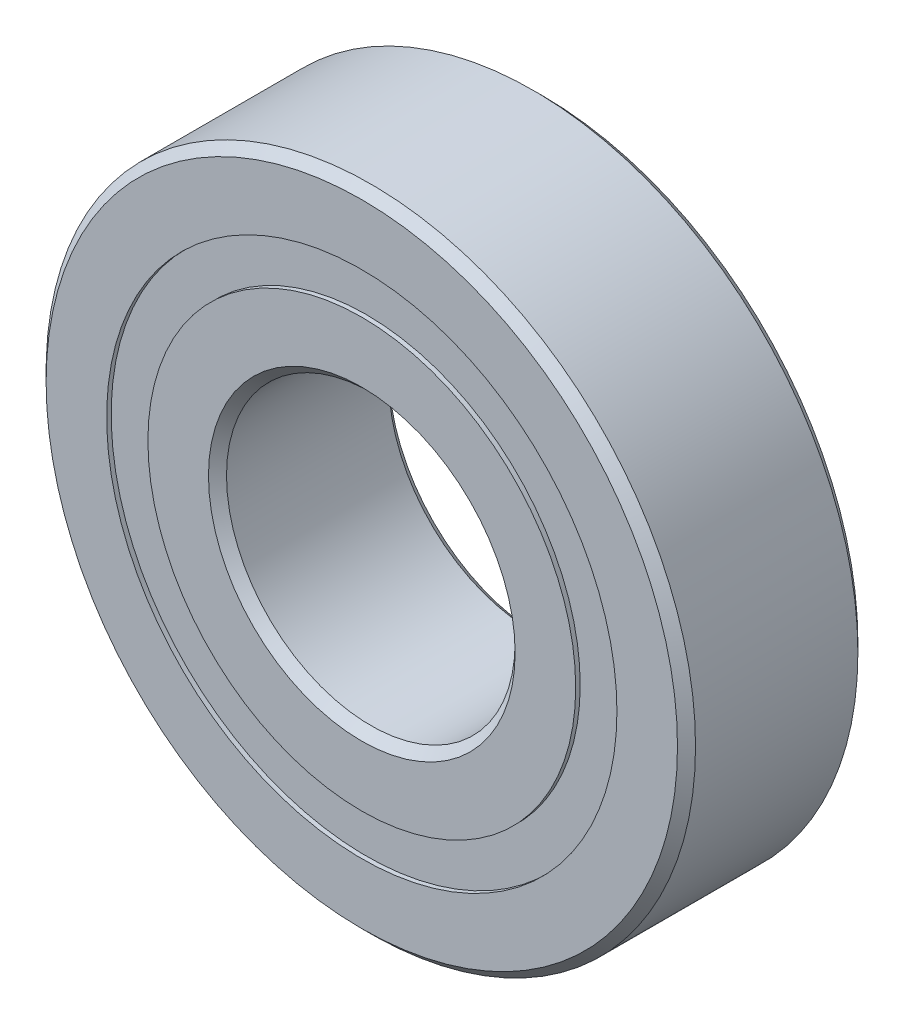
SolidWorks part; units mm, degrees
ref_plane "Front Plane" through (0, 0, 0) normal (0, 0, 1) x (1, 0, 0)
ref_plane "Top Plane" through (0, 0, 0) normal (0, 1, 0) x (1, 0, 0)
ref_plane "Right Plane" through (0, 0, 0) normal (1, 0, 0) x (0, 0, -1)
sketch "Sketch1" plane through (0, 0, 0) normal (1, 0, 0) x (0, 0, -1)
  line L0 (-3.9688, 0) -> (3.9688, 0) construction
  line L1 (0, 14.2875) -> (0, -14.2875) construction
  line L2 (3.5719, 14.2875) -> (-3.5719, 14.2875)
  line L3 (-3.5719, 14.2875) -> (-3.9688, 13.8906)
  line L4 (-3.9688, 13.8906) -> (-3.9688, 11.2259)
  line L5 (-3.9688, 11.2259) -> (-1.7639, 11.2259)
  line L6 (3.9687, 11.2259) -> (1.7639, 11.2259)
  line L7 (3.9687, 13.8906) -> (3.9687, 11.2259)
  line L8 (3.5719, 14.2875) -> (3.9687, 13.8906)
  line L9 (0, 14.2875) -> (0, 10.3187) construction
  line L10 (0, 10.3187) -> (0, 6.35) construction
  arc A0 (-1.7639, 11.2259) -> (1.7639, 11.2259) centre (0, 10.3187) cw
  point P14 (0, 6.35)
  dimension "Width" = 7.9375
  dimension "OD" = 28.575
  dimension "D1" = 45
  dimension "D2" = 0.3969
  dimension "Shaft Dia" = 12.7
  dimension "D3" = 3.5278
  dimension "D4" = 0.9071
revolve "Revolve1" add sketch "Sketch1" angle 360 about L0
sketch "Sketch3" plane through (0, 0, 0) normal (1, 0, 0) x (0, 0, -1)
  line L0 (-3.9688, 9.4116) -> (-1.7639, 9.4116)
  line L1 (0, 14.2875) -> (0, -14.2875) construction
  line L2 (-3.9688, 13.8906) -> (-3.9688, 11.2259) construction
  line L3 (-3.9688, 9.4116) -> (-3.9688, 6.7469)
  line L4 (-3.5719, 14.2875) -> (-3.9688, 13.8906) construction
  line L5 (-3.9688, 6.7469) -> (-3.5719, 6.35)
  line L6 (-3.5719, 6.35) -> (3.5719, 6.35)
  line L7 (3.5719, 14.2875) -> (3.5719, -14.2875) construction
  line L8 (3.5719, 6.35) -> (3.9688, 6.7469)
  line L9 (3.9688, -13.8906) -> (3.9688, 13.8906) construction
  line L10 (3.9688, 6.7469) -> (3.9688, 9.4116)
  line L11 (3.9688, 9.4116) -> (1.7639, 9.4116)
  line L13 (3.5719, 14.2875) -> (3.9687, 13.8906) construction
  arc A0 (1.7639, 11.2259) -> (-1.7639, 11.2259) centre (0, 10.3187) ccw construction
  arc A1 (1.7639, 9.4116) -> (-1.7639, 9.4116) centre (0, 10.3187) cw
revolve "Revolve3" add sketch "Sketch3" angle 360 about L0
sketch "Sketch4" plane through (0, 0, 0) normal (1, 0, 0) x (0, 0, -1)
  line L0 (-1.9835, 10.3187) -> (1.9835, 10.3187)
  arc A2 (-1.9835, 10.3187) -> (1.9835, 10.3187) centre (0, 10.3187) cw
  arc A3 (1.7639, 11.2259) -> (-1.7639, 11.2259) centre (0, 10.3187) ccw construction
revolve "Revolve4" add sketch "Sketch4" angle 360 about L0
ref_axis "Axis1" through (0, 0, -3.9688) along (0, 0, 1)
pattern_circular "CirPattern1" count 10 every 36 about axis through (0, 0, -3.9688) along (0, 0, 1) of bodies 104
sketch "Sketch5" plane through (0, 0, 0) normal (1, 0, 0) x (0, 0, -1)
  line L0 (-3.9688, 11.2259) -> (-1.7639, 11.2259) construction
  line L1 (-3.7703, 11.2259) -> (-1.9835, 11.2259)
  line L2 (-3.7703, 11.2259) -> (-3.7703, 9.4116)
  line L3 (-3.7703, 9.4116) -> (-1.9835, 9.4116)
  line L4 (-1.9835, 11.2259) -> (-1.9835, 9.4116)
  line L5 (-3.9688, 9.4116) -> (-1.7639, 9.4116) construction
  line L6 (3.9687, 11.2259) -> (1.7639, 11.2259) construction
  line L7 (3.7703, 11.2259) -> (1.9835, 11.2259)
  line L8 (3.7703, 11.2259) -> (3.7703, 9.4116)
  line L9 (3.7703, 9.4116) -> (1.9835, 9.4116)
  line L10 (1.9835, 11.2259) -> (1.9835, 9.4116)
  line L11 (3.9688, 9.4116) -> (1.7639, 9.4116) construction
  line L12 (-3.5719, 14.2875) -> (-3.9688, 13.8906) construction
  point P18 (-3.7703, 14.0891)
revolve "Revolve5" add sketch "Sketch5" angle 360 about L0
equation "\"D2@Sketch1\" = \"Width@Sketch1\"*.05"
equation "\"D3@Sketch1\" = \"Width@Sketch1\"/2.25"
equation "\"D4@Sketch1\" = (((\"OD@Sketch1\"-\"Width@Sketch1\")/2)/3.25)/3.5"
equation "\"D2@CirPattern1\" = 360/\"Balls@CirPattern1\""
